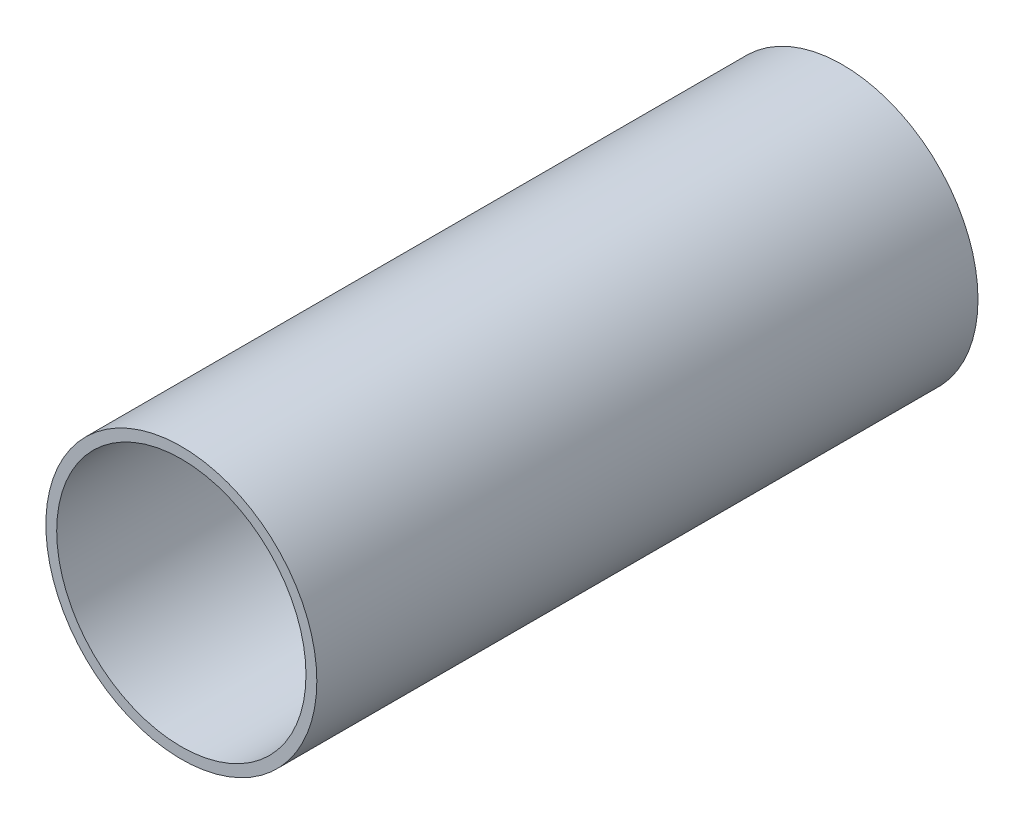
SolidWorks part; units mm, degrees
material "Plain Carbon Steel"
ref_plane "Front Plane" through (0, 0, 0) normal (0, 0, 1) x (1, 0, 0)
ref_plane "Top Plane" through (0, 0, 0) normal (0, 1, 0) x (1, 0, 0)
ref_plane "Right Plane" through (0, 0, 0) normal (1, 0, 0) x (0, 0, -1)
sketch "Sketch1" plane through (0, 0, 0) normal (0, 0, 1) x (1, 0, 0)
  circle A0 centre (0, 0) radius 73.025
  circle A1 centre (0, 0) radius 76.2
  circle A2 centre (0, 0) radius 79.375
  dimension "D1" = 3.175
  dimension "D2" = 146.05
  dimension "D3" = 3.175
extrude "Boss-Extrude1" add sketch "Sketch1" against normal blind 241.3 contours A1 A0 region at (-74.0447, 0, 0)
extrude "Boss-Extrude2" add sketch "Sketch1<3>" against normal blind 387.35 contours A2 A1 region at (-77.1299, 0, 0)
sketch "Sketch1<3>" plane through (0, 0, 0) normal (0, 0, 1) x (1, 0, 0) same geometry as "Sketch1"
